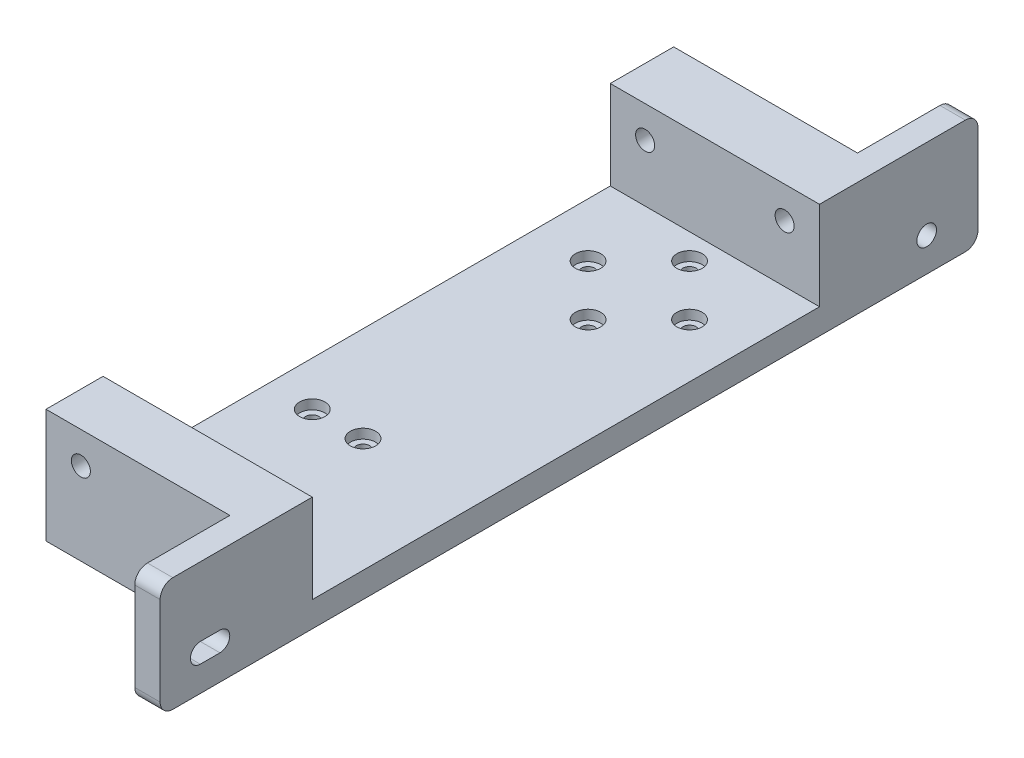
SolidWorks part; units mm, degrees
ref_plane "Front Plane" through (0, 0, 0) normal (0, 0, 1) x (1, 0, 0)
ref_plane "Top Plane" through (0, 0, 0) normal (0, 1, 0) x (1, 0, 0)
ref_plane "Right Plane" through (0, 0, 0) normal (1, 0, 0) x (0, 0, -1)
sketch "Sketch1" plane through (0, 0, 0) normal (0, 1, 0) x (1, 0, 0)
  line L0 (25, -34) -> (25, 0)
  line L1 (25, 0) -> (0, 0)
  line L2 (0, 0) -> (0, -34)
  line L3 (0, -34) -> (25, -34)
  arc A0 (20.5, -15.95) -> (20.5, -18.05) centre (20.5, -17) ccw
  arc A1 (20.5, -18.05) -> (20.5, -15.95) centre (20.5, -17) ccw
  arc A4 (12.5, -26.05) -> (12.5, -23.95) centre (12.5, -25) ccw
  arc A5 (12.5, -23.95) -> (12.5, -26.05) centre (12.5, -25) ccw
  arc A8 (4.5, -15.95) -> (4.5, -18.05) centre (4.5, -17) ccw
  arc A9 (4.5, -18.05) -> (4.5, -15.95) centre (4.5, -17) ccw
  arc A12 (12.5, -7.95) -> (12.5, -10.05) centre (12.5, -9) ccw
  arc A13 (12.5, -10.05) -> (12.5, -7.95) centre (12.5, -9) ccw
extrude "Boss-Extrude2" add sketch "Sketch1" along normal blind 4
sketch "Sketch2" plane through (0, 0, 0) normal (0, 0, -1) x (-1, 0, 0)
  line L2 (-25, 0) -> (0, 0)
  line L4 (-25, 4) -> (-25, 11.0849) construction
  line L5 (0, 4) -> (0, 10.8837) construction
  line L6 (-25, 0) -> (-29, 0)
  line L7 (-29, 0) -> (-29, 18)
  line L8 (-29, 18) -> (4, 18)
  line L9 (-12.5, 12) -> (-12.5, 15.32) construction
  line L10 (0, 0) -> (4, 0)
  line L11 (4, 0) -> (4, 18)
  circle A0 centre (-23.5, 13) radius 1.5
  circle A1 centre (-1.5, 13) radius 1.5
  point P18 (-12.5, 18)
  dimension "D1" = 18
  dimension "D2" = 13
  dimension "D3" = 13
extrude "Boss-Extrude3" add sketch "Sketch2" against normal blind 5
sketch "Sketch3" plane through (0, 0, 0) normal (0, 0, -1) x (-1, 0, 0)
  circle A0 centre (-1.5, 13) radius 1.5
  circle A1 centre (-23.5, 13) radius 1.5
extrude "Boss-Extrude4" add sketch "Sketch3" against normal blind 2
sketch "Sketch5" plane through (0, 0, 34) normal (0, 0, 1) x (1, 0, 0)
  line L8 (25, 0) -> (0, 0)
  line L9 (0, 4) -> (0, 0)
  line L11 (25, 0) -> (25, 4)
  line L12 (0, 4) -> (25, 4)
  line L13 (25, 4) -> (0, 4)
  line L14 (25, 0) -> (25, 4)
  line L16 (0, 4) -> (0, 0)
  line M16 (0, 0) -> (25, 0)
  line M17 (25, 0) -> (25, 4)
  line M18 (25, 4) -> (0, 4)
  line M19 (0, 4) -> (0, 0)
extrude "Boss-Extrude5" add sketch "Sketch5" along normal blind 55 contours M19 M16 M17 M18 region at (12.5, 2, 34)
sketch "Sketch6" plane through (0, 0, 89) normal (0, 0, 1) x (1, 0, 0)
  line L0 (0, 0) -> (-4, 0)
  line L1 (-4, 18) -> (-4, 0)
  line L2 (29, 0) -> (29, 18)
  line L3 (29, 0) -> (25, 0)
  line L4 (25, 0) -> (0, 0)
  line L5 (0, 4) -> (0, 0)
  line L6 (25, 0) -> (25, 4)
  line L7 (0, 4) -> (25, 4)
  line L8 (25, 4) -> (0, 4)
  line L9 (25, 0) -> (25, 4)
  line L10 (-4, 18) -> (29, 18)
  line L11 (0, 4) -> (0, 0)
  circle A0 centre (23.5, 13) radius 1.5
  circle A1 centre (1.5, 13) radius 1.5
  line M1 (0, 4) -> (0, 0)
  line M2 (0, 0) -> (25, 0)
  line M3 (25, 0) -> (25, 4)
  line M4 (25, 4) -> (0, 4)
  dimension "D1" = 18
  dimension "D2" = 13
  dimension "D3" = 13
extrude "Boss-Extrude6" add sketch "Sketch6" against normal blind 4 contours L10 L1 L0 L3 L2 A0 A1 M1 M4 M3 | M4 M1 M2 M3 region at (12.5, 2, 89) region at (12.5, 10.3409, 89)
sketch "Sketch7" plane through (0, 0, 0) normal (0, -1, 0) x (-1, 0, 0)
  line L1 (4, -85) -> (0, -85)
  line L2 (4, -85) -> (4, -5)
  line L3 (4, -5) -> (0, -5)
  line L4 (0, -85) -> (0, -5)
  line L5 (-25, -5) -> (-29, -5)
  line L6 (-25, -5) -> (-25, -85)
  line L7 (-25, -85) -> (-29, -85)
  line L8 (-29, -5) -> (-29, -85)
extrude "Boss-Extrude7" add sketch "Sketch7" against normal up to surface (4 mm away) up to face at (4.5, 4, 18.05)
sketch "Sketch9" plane through (0, 4, 0) normal (0, 1, 0) x (1, 0, 0)
  arc A0 (1.95, -59) -> (4.05, -59) centre (3, -59) ccw
  arc A1 (4.05, -59) -> (1.95, -59) centre (3, -59) ccw
  arc A2 (12.05, -59) -> (9.95, -59) centre (11, -59) ccw
  arc A3 (9.95, -59) -> (12.05, -59) centre (11, -59) ccw
  arc A4 (12.05, -75) -> (9.95, -75) centre (11, -75) ccw
  arc A5 (9.95, -75) -> (12.05, -75) centre (11, -75) ccw
  arc A6 (4.05, -75) -> (1.95, -75) centre (3, -75) ccw
  arc A7 (1.95, -75) -> (4.05, -75) centre (3, -75) ccw
extrude "Cut-Extrude2" cut sketch "Sketch9" against normal through all
sketch "Sketch10" plane through (0, 4, 0) normal (0, 1, 0) x (1, 0, 0)
  circle A0 centre (11, -75) radius 2
  circle A1 centre (3, -75) radius 2
  circle A2 centre (11, -59) radius 2
  circle A3 centre (3, -59) radius 2
  dimension "D1" = 4
extrude "Cut-Extrude3" cut sketch "Sketch10" against normal blind 1.5
sketch "Sketch11" plane through (0, 4, 0) normal (0, 1, 0) x (1, 0, 0)
  circle A0 centre (4.5, -17) radius 2
  circle A1 centre (12.5, -25) radius 2
  circle A2 centre (20.5, -17) radius 2
  circle A3 centre (12.5, -9) radius 2
extrude "Cut-Extrude4" cut sketch "Sketch11" against normal blind 1.5
sketch "Sketch14" plane through (29, 0, 0) normal (1, 0, 0) x (0, 0, -1)
  line L0 (-89, 0) -> (-89, 18)
  line L2 (-109, 18) -> (-109, 0)
  line L3 (-109, 18) -> (-89, 18)
  line L4 (-89, 0) -> (-109, 0)
  line L6 (-102.6662, 7.1133) -> (-99.5662, 7.1133)
  line L7 (-102.6662, 4.0133) -> (-99.5662, 4.0133)
  arc A2 (-102.6662, 7.1133) -> (-102.6662, 4.0133) centre (-102.6662, 5.5633) ccw
  arc A3 (-99.5662, 4.0133) -> (-99.5662, 7.1133) centre (-99.5662, 5.5633) ccw
extrude "Boss-Extrude8" add sketch "Sketch14" against normal blind 4
sketch "Sketch15" plane through (-4, 0, 0) normal (-1, 0, 0) x (0, 0, 1)
  line L0 (109, 0) -> (89, 0) construction
  line L1 (89, 18) -> (94, 18)
  line L2 (89, 18) -> (89, 0)
  line L3 (89, 0) -> (94, 0)
  line L4 (94, 18) -> (94, 0)
  dimension "D1" = 5
extrude "Boss-Extrude9" add sketch "Sketch15" against normal up to surface (29 mm away) up to face at (25, 5.5633, 101.1162)
extrude "Cut-Extrude5" cut sketch "Sketch6<3>" along normal blind 35 contours A0 | A1 region at (23.5, 13, 89) region at (1.5, 13, 89)
sketch "Sketch6<3>" plane through (0, 0, 89) normal (0, 0, 1) x (1, 0, 0) same geometry as "Sketch6"
fillet "Fillet2" radius 2 2 edges at (27, 18, 109) (27, 0, 109)
sketch "Sketch16" plane through (29, 0, 0) normal (1, 0, 0) x (0, 0, -1)
  line L0 (0, 18) -> (0, 0)
  line L1 (0, 18) -> (20, 18)
  line L2 (20, 0) -> (20, 18)
  line L4 (20, 0) -> (0, 0)
extrude "Boss-Extrude10" add sketch "Sketch16" against normal blind 4
sketch "Sketch17" plane through (-4, 0, 0) normal (-1, 0, 0) x (0, 0, 1)
  line L0 (0, 0) -> (-20, 0) construction
  line L1 (0, 18) -> (-5, 18)
  line L2 (0, 18) -> (0, 0)
  line L3 (0, 0) -> (-5, 0)
  line L4 (-5, 18) -> (-5, 0)
  dimension "D1" = 5
extrude "Boss-Extrude11" add sketch "Sketch17" against normal up to next
fillet "Fillet3" radius 2 2 edges at (27, 0, -20) (27, 18, -20)
sketch "Sketch18" plane through (25, 0, 0) normal (-1, 0, 0) x (0, 0, 1)
  circle A0 centre (-11.9048, 5.2958) radius 1.55
extrude "Cut-Extrude6" cut sketch "Sketch18" against normal through all
